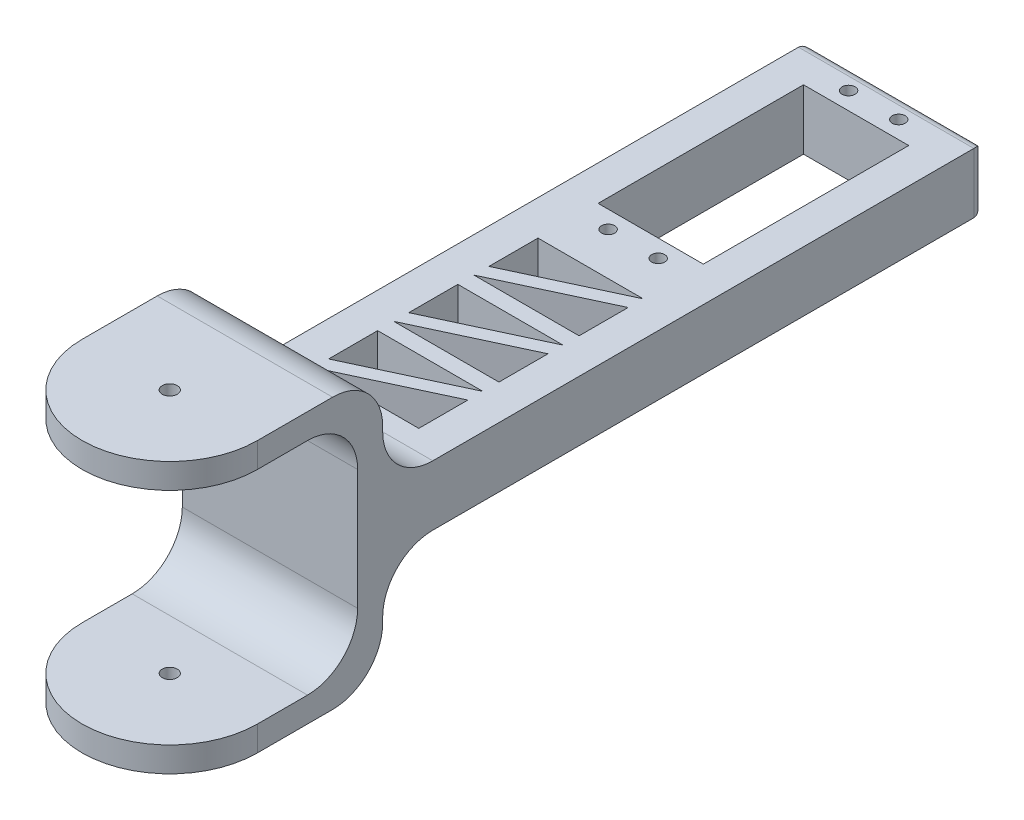
SolidWorks part; units mm, degrees
ref_plane "Front Plane" through (0, 0, 0) normal (0, 0, 1) x (1, 0, 0)
ref_plane "Top Plane" through (0, 0, 0) normal (0, 1, 0) x (1, 0, 0)
ref_plane "Right Plane" through (0, 0, 0) normal (1, 0, 0) x (0, 0, -1)
sketch "Sketch1" plane through (0, 0, 0) normal (0, 1, 0) x (1, 0, 0)
  line L2 (-17.5, 0) -> (-17.5, 20)
  line L3 (-17.5, 20) -> (17.5, 20)
  line L4 (17.5, 0) -> (17.5, 20)
  circle A0 centre (0, 0) radius 17.5
  circle A1 centre (0, 0) radius 1.5
  dimension "D1" = 35
  dimension "D2" = 3
  dimension "D3" = 20
  dimension "D4" = 35
extrude "Boss-Extrude1" add sketch "Sketch1" along normal blind 5 contours A0 A1 | A0 L4 L3 L2 region at (-17.0969, 0, -10) region at (0, 0, -17.005)
ref_plane "Plane1" through (0, -49, 0) normal (0, 1, 0) x (1, 0, 0)
sketch "Sketch3" plane through (0, -49, 0) normal (0, 1, 0) x (1, 0, 0)
  line L3 (17.5, 0) -> (17.5, 20)
  line L4 (17.5, 20) -> (-17.5, 20)
  line L5 (-17.5, 20) -> (-17.5, 0)
  line L6 (17.5, 0) -> (17.5, 20)
  line L7 (17.5, 20) -> (-17.5, 20)
  line L8 (-17.5, 20) -> (-17.5, 0)
  circle A0 centre (0, 0) radius 1.5 construction
  arc A1 (-17.5, 0) -> (17.5, 0) centre (0, 0) ccw
  arc A2 (-17.5, 0) -> (17.5, 0) centre (0, 0) ccw
  circle A3 centre (0, 0) radius 1.5
  dimension "D1" = 0
extrude "Boss-Extrude2" add sketch "Sketch3" along normal blind 5 separate body
sketch "Sketch4" plane through (0, 0, -20) normal (0, 0, -1) x (-1, 0, 0)
  line L0 (19.25, -49) -> (-19.25, -49) construction
  line L1 (-17.5, 5) -> (17.5, 5)
  line L2 (-17.5, 5) -> (-17.5, -49)
  line L3 (-17.5, -49) -> (17.5, -49)
  line L4 (17.5, 5) -> (17.5, -49)
  line L5 (17.5, -44) -> (17.5, -49) construction
extrude "Boss-Extrude3" add sketch "Sketch4" along normal blind 5
fillet "Fillet1" radius 10 4 edges at (0, -49, -25) (0, 5, -25) (0, -44, -20) (0, 0, -20)
sketch "Sketch6" plane through (0, 0, -25) normal (0, 0, -1) x (-1, 0, 0)
  line L0 (-17.5, -5) -> (-17.5, -39) construction
  line L1 (-17.5, -16) -> (17.5, -16)
  line L2 (-17.5, -16) -> (-17.5, -28)
  line L3 (-17.5, -28) -> (17.5, -28)
  line L4 (17.5, -16) -> (17.5, -28)
  line L5 (17.5, -39) -> (17.5, -5) construction
  line L6 (17.5, -5) -> (-17.5, -5) construction
  line L7 (-17.5, -39) -> (17.5, -39) construction
  dimension "D1" = 11
  dimension "D2" = 11
extrude "Boss-Extrude4" add sketch "Sketch6" along normal blind 120
sketch "Sketch7" plane through (0, -16, 0) normal (0, 1, 0) x (1, 0, 0)
  line L0 (-17.5, 145) -> (17.5, 145) construction
  line L1 (-10.5, 137) -> (10.5, 137)
  line L2 (-10.5, 137) -> (-10.5, 96)
  line L3 (-10.5, 96) -> (10.5, 96)
  line L4 (10.5, 137) -> (10.5, 96)
  line L5 (17.5, 145) -> (17.5, 25) construction
  line L6 (0, 151.0886) -> (0, 78.4667) construction
  line L7 (-21.8229, 116.5) -> (22.9186, 116.5) construction
  circle A0 centre (-5, 140.5) radius 1.3
  circle A1 centre (5, 140.5) radius 1.3
  circle A2 centre (5, 92.5) radius 1.3
  circle A3 centre (-5, 92.5) radius 1.3
  point P17 (-5.5832, 137)
  dimension "D5" = 2.6
  dimension "D1" = 8
  dimension "D2" = 21
  dimension "D3" = 41
  dimension "D4" = 7
  dimension "D6" = 3.5
  dimension "D7" = 5
extrude "Cut-Extrude1" cut sketch "Sketch7" against normal up to next
sketch "Sketch8" plane through (0, -16, 0) normal (0, 1, 0) x (1, 0, 0)
  line L0 (-17.5, 145) -> (-17.5, 25) construction
  line L1 (-10.5, 84) -> (10.5, 84)
  line L2 (-10.5, 84) -> (-10.5, 32)
  line L3 (-10.5, 32) -> (10.5, 32)
  line L4 (10.5, 84) -> (10.5, 32)
  line L5 (17.5, 145) -> (17.5, 25) construction
  line L6 (-17.5, 25) -> (17.5, 25) construction
  line L7 (-10.5, 96) -> (10.5, 96) construction
  line L8 (-10.5, 74.2075) -> (10.5, 84)
  line L9 (-10.5, 71.2075) -> (10.5, 81)
  line L10 (-10.5, 71.2075) -> (10.5, 71.2075)
  dimension "D1" = 7
  dimension "D2" = 7
  dimension "D3" = 7
  dimension "D4" = 12
  dimension "D5" = 25
  dimension "D6" = 3
extrude "Cut-Extrude2" cut sketch "Sketch8" against normal up to next contours L2 L8 L1 | L9 L10 L4 region at (-3.5, -16, -80.7358) region at (3.5, -16, -74.4717)
pattern_linear "LPattern1" count 3 spacing 16 along (0, 0, 1) of "Cut-Extrude2"
fillet "Fillet2" radius 10 2 edges at (0, -16, -25) (0, -28, -25)
fillet "Fillet3" radius 2 4 edges at (17.5, -22, -145) (-17.5, -22, -145) (0, -16, -145) (0, -28, -145)
